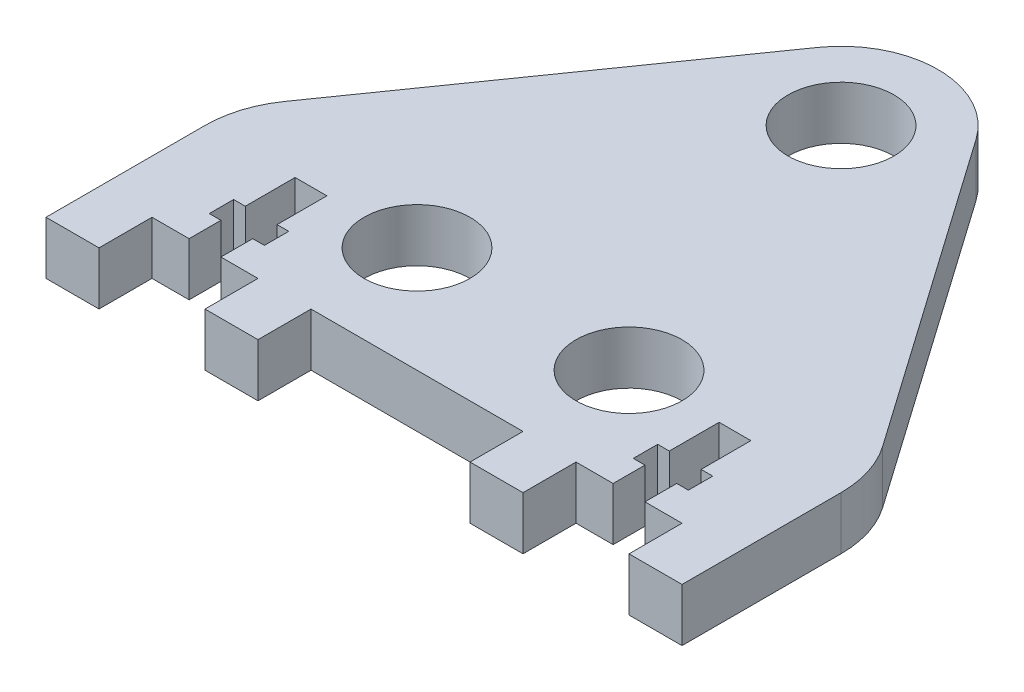
SolidWorks part; units mm, degrees
ref_plane "Front Plane" through (0, 0, 0) normal (0, 0, 1) x (1, 0, 0)
ref_plane "Top Plane" through (0, 0, 0) normal (0, 1, 0) x (1, 0, 0)
ref_plane "Right Plane" through (0, 0, 0) normal (1, 0, 0) x (0, 0, -1)
sketch "Sketch1" plane through (0, 0, 0) normal (0, 1, 0) x (1, 0, 0)
  line L0 (-7.6871, -11.3498) -> (-7.6871, -16.3498) construction
  line L1 (-27.6871, -1.3498) -> (-27.6871, -16.3498)
  line L2 (-27.6871, -16.3498) -> (-22.6871, -16.3498)
  line L3 (-7.6871, -16.3498) -> (-7.6871, -11.3498)
  line L4 (-7.6871, -11.3498) -> (12.3129, -11.3498)
  line L5 (12.3129, -16.3498) -> (12.3129, -11.3498)
  line L6 (32.3129, -16.3498) -> (27.3129, -16.3498)
  line L7 (32.3129, -1.3498) -> (32.3129, -16.3498)
  line L8 (12.3129, -11.3498) -> (12.3129, -16.3498) construction
  line L9 (-27.6871, -11.3498) -> (-27.6871, -16.3498) construction
  line L10 (32.3129, -11.3498) -> (32.3129, -16.3498) construction
  line L11 (2.3129, -11.3498) -> (2.3129, 43.6328) construction
  line L12 (32.3129, -16.3498) -> (12.3129, -16.3498) construction
  line L13 (-25.8745, 4.3919) -> (-5.1782, 33.9036)
  line L14 (9.804, 33.9036) -> (30.5002, 4.3919)
  line L36 (-22.6871, -16.3498) -> (-22.6871, -11.3498)
  line L37 (-22.6871, -11.3498) -> (-19.1871, -11.3498)
  line L38 (-19.1871, -11.3498) -> (-19.1871, -8.3498)
  line L39 (-19.1871, -8.3498) -> (-20.2871, -8.3498)
  line L40 (-20.2871, -8.3498) -> (-20.2871, -6.0498)
  line L41 (-20.2871, -6.0498) -> (-19.1871, -6.0498)
  line L42 (-19.1871, -6.0498) -> (-19.1871, -1.3498)
  line L43 (-19.1871, -1.3498) -> (-16.1871, -1.3498)
  line L44 (-16.1871, -1.3498) -> (-16.1871, -6.0498)
  line L45 (-16.1871, -6.0498) -> (-15.0871, -6.0498)
  line L46 (-15.0871, -6.0498) -> (-15.0871, -8.3498)
  line L47 (-15.0871, -8.3498) -> (-16.1871, -8.3498)
  line L48 (-16.1871, -8.3498) -> (-16.1871, -11.3498)
  line L49 (-16.1871, -11.3498) -> (-12.6871, -11.3498)
  line L50 (-12.6871, -11.3498) -> (-12.6871, -16.3498)
  line L51 (-12.6871, -16.3498) -> (-7.6871, -16.3498)
  line L52 (27.3129, -11.3498) -> (23.8129, -11.3498)
  line L53 (23.8129, -11.3498) -> (23.8129, -8.3498)
  line L54 (23.8129, -8.3498) -> (24.9129, -8.3498)
  line L55 (24.9129, -6.0498) -> (23.8129, -6.0498)
  line L56 (24.9129, -8.3498) -> (24.9129, -6.0498)
  line L57 (23.8129, -6.0498) -> (23.8129, -1.3498)
  line L58 (23.8129, -1.3498) -> (20.8129, -1.3498)
  line L59 (20.8129, -1.3498) -> (20.8129, -6.0498)
  line L60 (20.8129, -6.0498) -> (19.7129, -6.0498)
  line L61 (19.7129, -6.0498) -> (19.7129, -8.3498)
  line L62 (19.7129, -8.3498) -> (20.8129, -8.3498)
  line L63 (20.8129, -8.3498) -> (20.8129, -11.3498)
  line L64 (20.8129, -11.3498) -> (17.3129, -11.3498)
  line L65 (17.3129, -11.3498) -> (17.3129, -16.3498)
  line L66 (27.3129, -16.3498) -> (27.3129, -11.3498)
  line L67 (17.3129, -16.3498) -> (12.3129, -16.3498)
  arc A0 (-5.1782, 33.9036) -> (9.804, 33.9036) centre (2.3129, 28.6502) cw
  circle A2 centre (2.3129, 28.6502) radius 5
  arc A3 (32.3129, -1.3498) -> (30.5002, 4.3919) centre (22.3129, -1.3498) ccw
  arc A4 (-27.6871, -1.3498) -> (-25.8745, 4.3919) centre (-17.6871, -1.3498) cw
  circle A5 centre (-7.6871, -1.3498) radius 5
  circle A6 centre (12.3129, -1.3498) radius 5
  point P32 (0, 0)
  point P68 (-14.4371, -11.3498)
  point P72 (-15.6371, -8.3498)
  point P73 (-19.7371, -6.0498)
  point P74 (-19.7371, -8.3498)
  point P78 (24.3629, -8.3498)
  point P80 (24.3629, -6.0498)
  point P88 (20.2629, -8.3498)
  point P91 (19.0629, -11.3498)
  dimension "D1" = 5
  dimension "D4" = 10
  dimension "D24" = 10
  dimension "D2" = 5
  dimension "D3" = 40
  dimension "D5" = 10
  dimension "D12" = 5
  dimension "D13" = 5
  dimension "D14" = 10
  dimension "D15" = 2.3
  dimension "D16" = 3
  dimension "D17" = 10
  dimension "D18" = 3
  dimension "D19" = 3.5
  dimension "D20" = 5.2
  dimension "D21" = 2.6
  dimension "D22" = 10
  dimension "D23" = 10
extrude "Boss-Extrude1" add sketch "Sketch1" along normal blind 5
